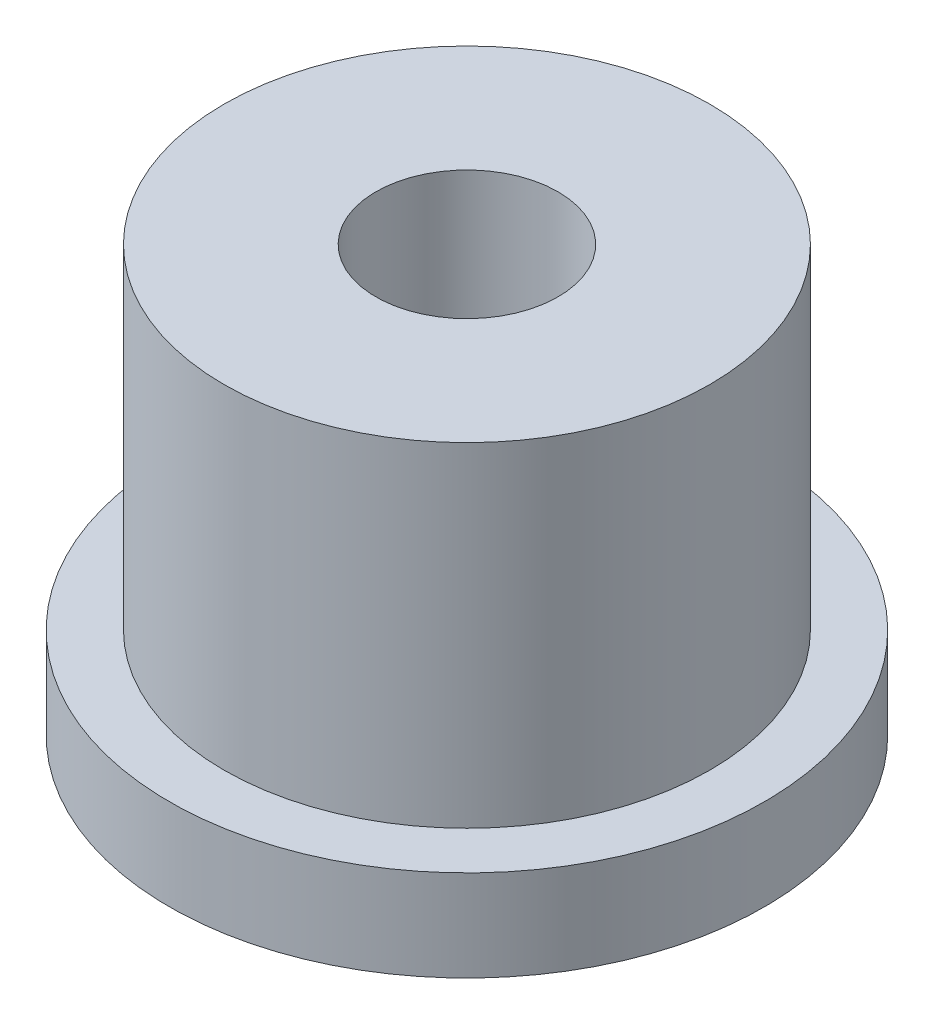
SolidWorks part; units mm, degrees
ref_plane "Przednia" through (0, 0, 0) normal (0, 0, 1) x (1, 0, 0)
ref_plane "Górna" through (0, 0, 0) normal (0, 1, 0) x (1, 0, 0)
ref_plane "Prawa" through (0, 0, 0) normal (1, 0, 0) x (0, 0, -1)
sketch "Szkic1" plane through (0, 0, 0) normal (0, 0, 1) x (1, 0, 0)
  line L0 (0, 0) -> (0, 32.239) construction
  line L1 (1.5, 2) -> (1.5, 7)
  line L2 (1.5, 7) -> (4, 7)
  line L3 (4, 7) -> (4, 1.5)
  line L4 (4, 1.5) -> (4.9, 1.5)
  line L5 (4.9, 1.5) -> (4.9, 0)
  line L6 (4.9, 0) -> (2.75, 0)
  line L7 (0, 0) -> (2.75, 0) construction
  line L8 (1.5, 2) -> (2.75, 2)
  line L9 (2.75, 2) -> (2.75, 0)
  dimension "D1" = 4
  dimension "D2" = 2.75
  dimension "D3" = 7
  dimension "D4" = 4.9
  dimension "D5" = 1.5
  dimension "D6" = 1.5
  dimension "D7" = 2
revolve "Obrót1" add sketch "Szkic1" angle 360 about L0
